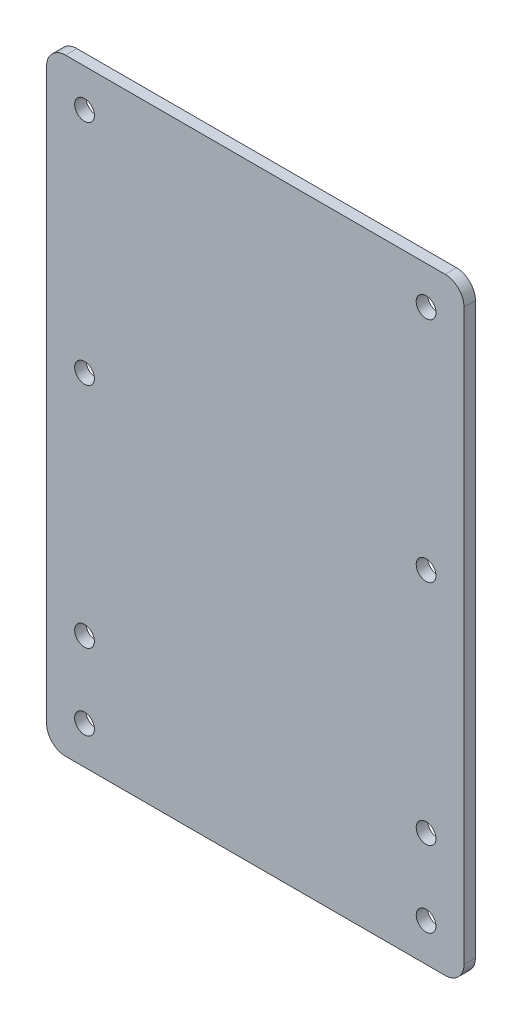
SolidWorks part; units mm, degrees
ref_plane "正面" through (0, 0, 0) normal (0, 0, 1) x (1, 0, 0)
ref_plane "平面" through (0, 0, 0) normal (0, 1, 0) x (1, 0, 0)
ref_plane "右側面" through (0, 0, 0) normal (1, 0, 0) x (0, 0, -1)
sketch "ｽｹｯﾁ2" plane through (0, 0, 0) normal (0, 0, 1) x (1, 0, 0)
  line L0 (0, -10) -> (110, -10) construction
  line L1 (0, 0) -> (110, 0)
  line L2 (0, 0) -> (0, -140)
  line L3 (0, -140) -> (110, -140)
  line L4 (110, 0) -> (110, -140)
  line L5 (0, -130) -> (110, -130) construction
  line L6 (10, -10) -> (10, -130) construction
  line L7 (100, -10) -> (100, -130) construction
  circle A0 centre (10, -10) radius 2.6
  circle A1 centre (100, -10) radius 2.6
  circle A2 centre (10, -130) radius 2.6
  circle A3 centre (100, -130) radius 2.6
  circle A4 centre (100, -70) radius 2.6
  circle A5 centre (10, -70) radius 2.6
  dimension "D4" = 5.2
  dimension "D5" = 10
  dimension "D6" = 10
  dimension "D7" = 120
  dimension "D1" = 10
  dimension "D2" = 110
  dimension "D8" = 10
extrude "ﾎﾞｽ - 押し出し1" add sketch "ｽｹｯﾁ2" along normal blind 3
sketch "ｽｹｯﾁ3" plane through (0, 0, 0) normal (0, 0, -1) x (-1, 0, 0)
  line L0 (0, 0) -> (0, -140) construction
  line L1 (-110, -140) -> (0, -140)
  line L2 (-110, -140) -> (-110, -160)
  line L3 (-110, -160) -> (0, -160)
  line L4 (0, -140) -> (0, -160)
  line L5 (-110, -150) -> (0, -150) construction
  line L6 (-100, -130) -> (-100, -150) construction
  line L7 (-10, -130) -> (-10, -150) construction
  circle A0 centre (-100, -150) radius 2.6
  circle A1 centre (-10, -150) radius 2.6
  circle A2 centre (-100, -130) radius 2.6 construction
  dimension "D1" = 20
extrude "ﾎﾞｽ - 押し出し2" add sketch "ｽｹｯﾁ3" against normal up to surface (3 mm away) up to face at (102.6, -70, 3)
fillet "ﾌｨﾚｯﾄ1" radius 5 4 edges at (110, 0, 1.5) (0, 0, 1.5) (0, -160, 1.5) (110, -160, 1.5)
